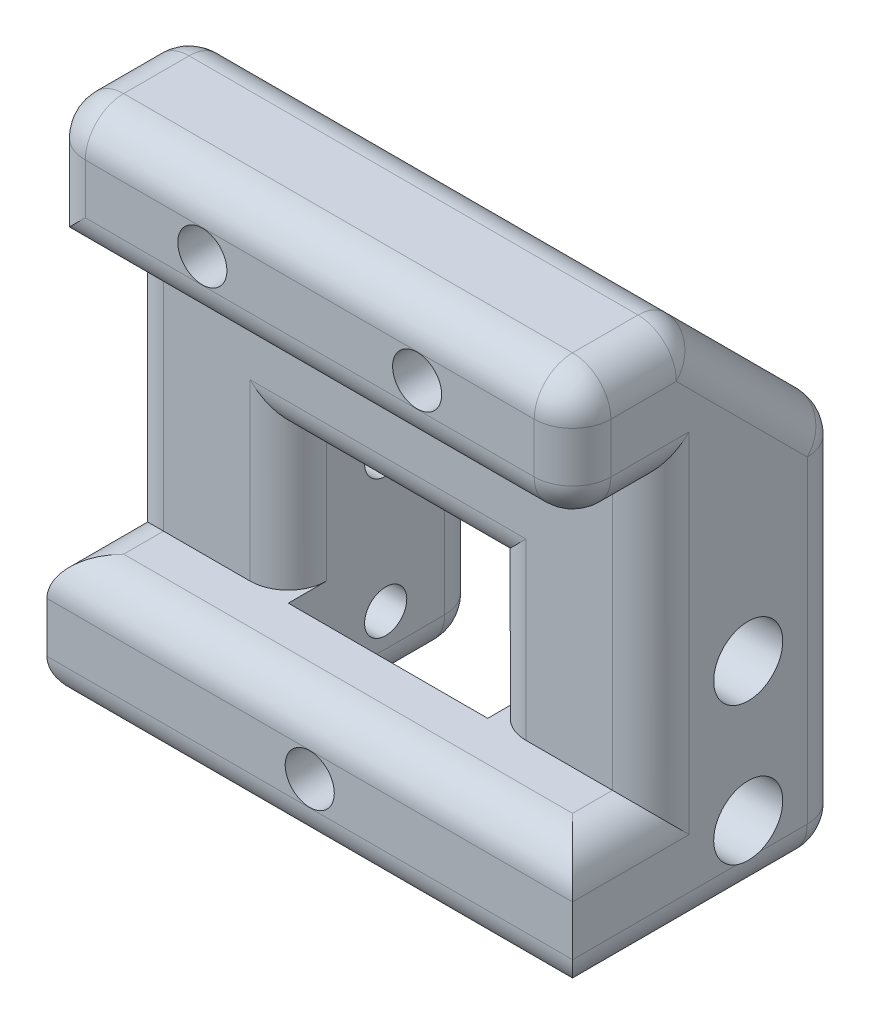
SolidWorks part; units mm, degrees
ref_plane "Front Plane" through (0, 0, 0) normal (0, 0, 1) x (1, 0, 0)
ref_plane "Top Plane" through (0, 0, 0) normal (0, 1, 0) x (1, 0, 0)
ref_plane "Right Plane" through (0, 0, 0) normal (1, 0, 0) x (0, 0, -1)
sketch "Sketch1" plane through (0, 0, 0) normal (0, 0, 1) x (1, 0, 0)
  line L1 (-34.26, 34.26) -> (34.26, 34.26)
  line L2 (-34.26, 34.26) -> (-34.26, -34.26)
  line L3 (-34.26, -34.26) -> (34.26, -34.26)
  line L4 (34.26, 34.26) -> (34.26, -34.26)
  point P4 (0, 34.26)
  point P6 (-34.26, 0)
  dimension "D1" = 68.52
extrude "Boss-Extrude1" add sketch "Sketch1" along normal blind 35.6
sketch "Sketch2" plane through (0, 0, 35.6) normal (0, 0, 1) x (1, 0, 0)
  line L0 (-34.26, 34.26) -> (-34.26, -34.26) construction
  line L1 (-34.26, -17.74) -> (34.26, -17.74)
  line L2 (-34.26, -17.74) -> (-34.26, 17.74)
  line L3 (-34.26, 17.74) -> (34.26, 17.74)
  line L4 (34.26, -17.74) -> (34.26, 17.74)
  line L5 (34.26, -34.26) -> (34.26, 34.26) construction
  point P8 (34.26, 0)
  dimension "D1" = 35.48
extrude "Cut-Extrude1" cut sketch "Sketch2" against normal blind 10.2
sketch "Sketch3" plane through (0, 0, 35.6) normal (0, 0, 1) x (1, 0, 0)
  line L0 (-14, 26) -> (14, 26) construction
  line L1 (0, -26) -> (0, 26) construction
  circle A0 centre (-14, 26) radius 3.2
  circle A1 centre (14, 26) radius 3.2
  circle A2 centre (0, -26) radius 3.2
  point P6 (0, 26)
  point P8 (0, 0)
  dimension "D2" = 6.4
  dimension "D3" = 6.4
  dimension "D4" = 6.4
  dimension "D1" = 52
  dimension "D5" = 28
extrude "Cut-Extrude2" cut sketch "Sketch3" against normal blind 10.2
sketch "Sketch4" plane through (0, 0, 0) normal (0, 0, -1) x (-1, 0, 0)
  line L0 (34.26, -34.26) -> (-34.26, -34.26) construction
  line L1 (-13, -34.26) -> (13, -34.26)
  line L2 (-13, -34.26) -> (-13, 0)
  line L3 (-13, 0) -> (13, 0)
  line L4 (13, -34.26) -> (13, 0)
  point P6 (0, 0)
  dimension "D1" = 26
extrude "Cut-Extrude3" cut sketch "Sketch4" against normal blind 25.4
sketch "Sketch6" plane through (34.26, 0, 0) normal (1, 0, 0) x (0, 0, -1)
  line L0 (-25.4, 0) -> (0, 0) construction
  line L1 (-25.4, 0) -> (0, 0) construction
  circle A0 centre (-12.7, -7) radius 2.75
  circle A1 centre (-12.7, -25) radius 2.75
  point P7 (-12.7, 0)
  dimension "D2" = 5.5
  dimension "D3" = 5.5
  dimension "D1" = 7
  dimension "D4" = 25
extrude "Cut-Extrude4" cut sketch "Sketch6" against normal through all both and the other way through all
sketch "Sketch7" plane through (34.26, 0, 0) normal (1, 0, 0) x (0, 0, -1)
  circle A0 centre (-12.7, -7) radius 2.75 construction
  circle A1 centre (-12.7, -7) radius 2.75 construction
  circle A2 centre (-12.7, -7) radius 4.5
  circle A3 centre (-12.7, -25) radius 4.5
  dimension "D1" = 9
  dimension "D2" = 9
extrude "Cut-Extrude5" cut sketch "Sketch7" against normal offset from surface (13.26 mm away) 8 up to face at (13, -4.25, 12.7)
sketch "Sketch8" plane through (-34.26, 0, 0) normal (-1, 0, 0) x (0, 0, 1)
  circle A0 centre (12.7, -7) radius 4.5
  circle A1 centre (12.7, -25) radius 4.5
  dimension "D1" = 9
  dimension "D2" = 9
extrude "Cut-Extrude6" cut sketch "Sketch8" against normal offset from surface (13.26 mm away) 8 up to face at (-13, -9.75, 12.7)
chamfer "Chamfer1" distance 20 angle 45 1 edges at (0, 34.26, 0)
fillet "Fillet1" radius 5 32 edges at (-13, -34.26, 12.7) (-23.63, -34.26, 0) (-34.26, -34.26, 17.8) (0, -34.26, 35.6) (34.26, -34.26, 17.8) (23.63, -34.26, 0) (13, -34.26, 12.7) (0, -34.26, 25.4) (-34.26, -10, 0) (-13, -17.13, 0) (0, 0, 0) (13, -17.13, 0) (34.26, -17.74, 30.5) (13, -8.87, 25.4) (-13, -8.87, 25.4) (0, 0, 25.4) (0, -17.74, 35.6) (-34.26, -17.74, 30.5) (-34.26, 0, 25.4) (0, 17.74, 35.6) (-34.26, 26, 35.6) (34.26, 26, 35.6) (34.26, 17.74, 30.5) (34.26, 0, 25.4) (34.26, -10, 0) (0, 14.26, 0) (34.26, 24.26, 10) (0, 34.26, 20) (0, 34.26, 35.6) (34.26, 34.26, 27.8) (-34.26, 34.26, 27.8) (-34.26, 24.26, 10)
